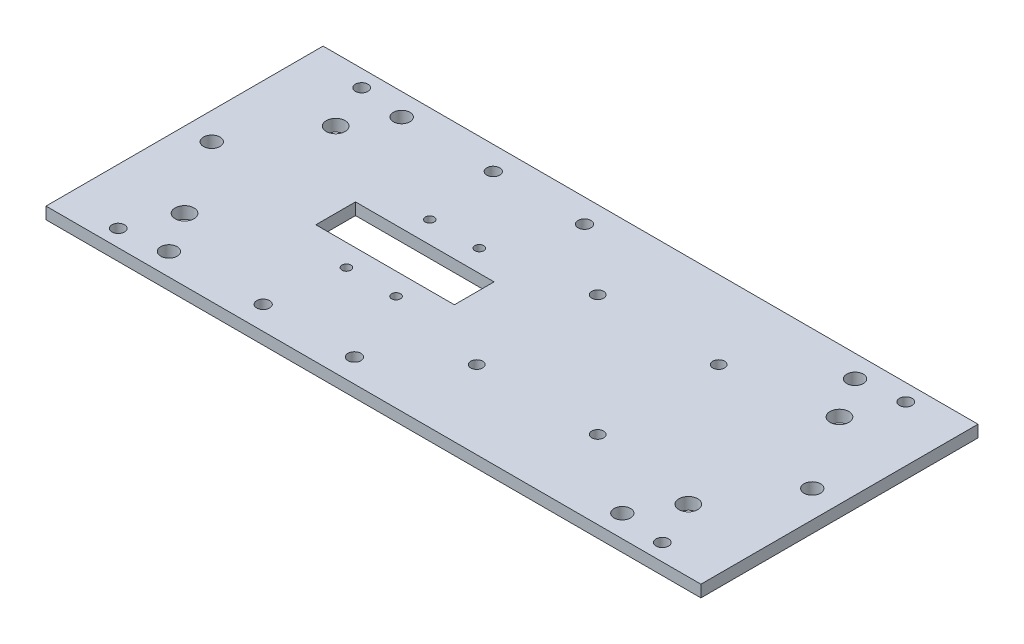
SolidWorks part; units mm, degrees
material "Thornel VCB-20 Carbon Cloth"
ref_plane "Front Plane" through (0, 0, 0) normal (0, 0, 1) x (1, 0, 0)
ref_plane "Top Plane" through (0, 0, 0) normal (0, 1, 0) x (1, 0, 0)
ref_plane "Right Plane" through (0, 0, 0) normal (1, 0, 0) x (0, 0, -1)
sketch "Sketch1" plane through (0, 0, 0) normal (0, 1, 0) x (1, 0, 0)
  line L0 (82.55, -34.925) -> (82.55, 34.925)
  line L1 (82.55, -34.925) -> (-82.55, -34.925)
  line L2 (82.55, 34.925) -> (-82.55, 34.925)
  line L3 (-82.55, -34.925) -> (-82.55, 34.925)
  line L4 (82.55, -34.925) -> (-82.55, 34.925) construction
  line L5 (82.55, 34.925) -> (-82.55, -34.925) construction
  point P1 (0, 0)
  dimension "D1" = 165.1
  dimension "D2" = 69.85
extrude "Boss-Extrude1" add sketch "Sketch1" along normal blind 3
sketch "Sketch6" plane through (0, 0, 0) normal (0, -1, 0) x (1, 0, 0)
  line L0 (-82.55, -34.925) -> (-82.55, 34.925) construction
  line L1 (-44.45, 5) -> (-9.525, 5)
  line L2 (-44.45, 5) -> (-44.45, -5)
  line L3 (-44.45, -5) -> (-9.525, -5)
  line L4 (-9.525, 5) -> (-9.525, -5)
  line L5 (-10.724, -29) -> (-33.726, -29) construction
  line L6 (-10.724, -29) -> (-10.724, 29) construction
  line L7 (-10.724, 29) -> (-33.726, 29) construction
  line L8 (-33.726, -29) -> (-33.726, 29) construction
  line L9 (-10.724, -29) -> (-33.726, 29) construction
  line L10 (-10.724, 29) -> (-33.726, -29) construction
  circle A0 centre (6.35, 15.25) radius 1.5
  circle A1 centre (36.85, 15.25) radius 1.5
  circle A2 centre (6.35, -15.25) radius 1.5
  circle A3 centre (36.85, -15.25) radius 1.5
  circle A4 centre (-33.726, 29) radius 1.625
  circle A5 centre (-10.724, 29) radius 1.625
  circle A6 centre (-10.724, -29) radius 1.625
  circle A7 centre (-33.726, -29) radius 1.625
  point P8 (-9.525, 0)
  point P18 (-22.225, 0)
  dimension "D5" = 3
  dimension "D6" = 3
  dimension "D7" = 3
  dimension "D8" = 3
  dimension "D18" = 3.25
  dimension "D1" = 34.925
  dimension "D2" = 10
  dimension "D3" = 38.1
  dimension "D4" = 30.5
  dimension "D9" = 30.5
  dimension "D10" = 30.5
  dimension "D11" = 15.25
  dimension "D12" = 6.35
  dimension "D13" = 15.25
  dimension "D14" = 15.25
  dimension "D15" = 15.25
  dimension "D16" = 58
  dimension "D17" = 23.002
  dimension "D19" = 60.325
  dimension "D20" = 0
extrude "Cut-Extrude1" cut sketch "Sketch6" against normal up to next contours A4 | L4 L1 L2 L3 A4 | A6 | A2 | A3 | A1 | A0 | A7 | A5 region at (-26.9875, 0, 0) region at (6.35, 0, 15.25) region at (36.85, 0, 15.25) region at (6.35, 0, -15.25) region at (36.85, 0, -15.25) region at (-33.726, 0, 29) region at (-10.724, 0, -29)
sketch "Sketch7" plane through (0, 3, 0) normal (0, 1, 0) x (1, 0, 0)
  line L0 (-82.55, 34.925) -> (-82.55, -34.925) construction
  line L1 (82.55, -34.925) -> (82.55, 34.925) construction
  line L2 (-82.55, -34.925) -> (82.55, -34.925) construction
  line L3 (82.55, 34.925) -> (-82.55, 34.925) construction
  circle A0 centre (-77.47, 29.845) radius 1.5
  circle A1 centre (-77.47, -29.845) radius 1.5
  circle A2 centre (77.47, -29.845) radius 1.5
  circle A3 centre (77.47, 29.845) radius 1.5
  dimension "D9" = 3
  dimension "D10" = 3
  dimension "D11" = 3
  dimension "D12" = 3
  dimension "D1" = 5.08
  dimension "D2" = 5.08
  dimension "D3" = 5.08
  dimension "D4" = 5.08
  dimension "D5" = 5.08
  dimension "D6" = 5.08
  dimension "D7" = 5.08
  dimension "D8" = 5.08
sketch "Sketch8" plane through (0, 3, 0) normal (0, 1, 0) x (1, 0, 0)
  line L0 (-82.55, -34.925) -> (82.55, -34.925) construction
  line L1 (-82.55, 34.925) -> (-82.55, -34.925) construction
  line L2 (82.55, -34.925) -> (82.55, 34.925) construction
  line L3 (82.55, 34.925) -> (-82.55, 34.925) construction
  circle A0 centre (-63.5, -19.05) radius 2.3813
  circle A1 centre (-63.5, 19.05) radius 2.3813
  circle A2 centre (63.5, 19.05) radius 2.3813
  circle A3 centre (63.5, -19.05) radius 2.3813
  dimension "D1" = 4.7625
  dimension "D4" = 4.7625
  dimension "D5" = 4.7625
  dimension "D6" = 4.7625
  dimension "D2" = 15.875
  dimension "D3" = 19.05
  dimension "D7" = 19.05
  dimension "D8" = 19.05
  dimension "D9" = 19.05
  dimension "D10" = 15.875
  dimension "D11" = 15.875
  dimension "D12" = 15.875
extrude "Cut-Extrude3" cut sketch "Sketch8" against normal up to next
sketch "Sketch9" plane through (0, 3, 0) normal (0, 1, 0) x (1, 0, 0)
  line L0 (-82.55, 34.925) -> (-82.55, -34.925) construction
  line L1 (82.55, -34.925) -> (82.55, 34.925) construction
  circle A0 centre (-75.692, 0) radius 2.0828
  circle A1 centre (75.692, 0) radius 2.0828
  dimension "D1" = 6.858
  dimension "D2" = 6.858
extrude "Cut-Extrude5" cut sketch "Sketch9" against normal blind 5.08
sketch "Sketch10" plane through (0, 3, 0) normal (0, 1, 0) x (1, 0, 0)
  line L0 (-82.55, -34.925) -> (82.55, -34.925) construction
  line L1 (82.55, 34.925) -> (-82.55, 34.925) construction
  circle A0 centre (0, -29.337) radius 2.0828
  circle A1 centre (0, 29.337) radius 2.0828
  circle A2 centre (57.15, -29.337) radius 2.0828
  circle A3 centre (57.15, 29.337) radius 2.0828
  circle A4 centre (-57.15, -29.337) radius 2.0828
  circle A5 centre (-57.15, 29.337) radius 2.0828
  point P8 (0, 0)
  dimension "D1" = 5.588
  dimension "D2" = 5.588
  dimension "D3" = 2
  dimension "D4" = 2
extrude "Cut-Extrude6" cut sketch "Sketch10" against normal blind 5.08 contours A5 | A2 | A3 | A4 region at (57.15, 3, 29.337) region at (57.15, 3, -29.337) region at (-57.15, 3, 29.337) region at (-57.15, 3, -29.337)
sketch "Sketch11" plane through (0, 3, 0) normal (0, 1, 0) x (1, 0, 0)
  line L1 (-18.7375, 10.5) -> (-31.2375, 10.5) construction
  line L2 (-18.7375, 10.5) -> (-18.7375, -10.5) construction
  line L3 (-18.7375, -10.5) -> (-31.2375, -10.5) construction
  line L4 (-31.2375, 10.5) -> (-31.2375, -10.5) construction
  line L5 (-18.7375, 10.5) -> (-31.2375, -10.5) construction
  line L6 (-18.7375, -10.5) -> (-31.2375, 10.5) construction
  line L7 (-9.525, 5) -> (-44.45, 5) construction
  circle A0 centre (-31.2375, 10.5) radius 1.125
  circle A1 centre (-18.7375, 10.5) radius 1.125
  circle A2 centre (-18.7375, -10.5) radius 1.125
  circle A3 centre (-31.2375, -10.5) radius 1.125
  point P0 (-24.9875, 0)
  point P9 (-26.9875, 5)
  dimension "D4" = 2.25
  dimension "D5" = 2.25
  dimension "D6" = 2.25
  dimension "D7" = 2.25
  dimension "D1" = 12.5
  dimension "D2" = 21
  dimension "D3" = 2
extrude "Cut-Extrude7" cut sketch "Sketch11" against normal blind 41.91
sketch "Sketch12" plane through (0, 0, 0) normal (0, -1, 0) x (1, 0, 0)
  line L0 (-24.5963, 23.3735) -> (-5.5463, 23.3735) construction
  line L1 (-24.5963, 24.5641) -> (-5.5463, 24.5641)
  line L2 (-24.5963, 24.5641) -> (-24.5963, 22.1829)
  line L3 (-24.5963, 22.1829) -> (-5.5463, 22.1829)
  line L4 (-5.5463, 24.5641) -> (-5.5463, 22.1829)
  line L5 (-15.0713, 24.5641) -> (-15.0713, 22.1829)
  line L6 (0.8037, 24.5641) -> (0.8037, 22.1829)
  line L7 (0.8037, 24.5641) -> (19.8537, 24.5641)
  line L8 (19.8537, 24.5641) -> (19.8537, 22.1829)
  line L9 (0.8037, 22.1829) -> (19.8537, 22.1829)
  line L10 (26.2037, 24.5641) -> (26.2037, 22.1829)
  line L11 (26.2037, 24.5641) -> (45.2537, 24.5641)
  line L12 (45.2537, 24.5641) -> (45.2537, 22.1829)
  line L13 (26.2037, 22.1829) -> (45.2537, 22.1829)
  line L14 (0.8037, 9.3241) -> (0.8037, 6.9429)
  line L15 (0.8037, 9.3241) -> (19.8537, 9.3241)
  line L16 (19.8537, 9.3241) -> (19.8537, 6.9429)
  line L17 (0.8037, 6.9429) -> (19.8537, 6.9429)
  line L18 (26.2037, 9.3241) -> (26.2037, 6.9429)
  line L19 (26.2037, 9.3241) -> (45.2537, 9.3241)
  line L20 (45.2537, 9.3241) -> (45.2537, 6.9429)
  line L21 (26.2037, 6.9429) -> (45.2537, 6.9429)
  line L22 (-24.5963, 9.3241) -> (-24.5963, 6.9429)
  line L23 (-24.5963, 9.3241) -> (-5.5463, 9.3241)
  line L24 (-5.5463, 9.3241) -> (-5.5463, 6.9429)
  line L25 (-24.5963, 6.9429) -> (-5.5463, 6.9429)
  line L26 (-24.5963, 24.5641) -> (0.8037, 24.5641) construction
  line L27 (-71.2714, 9.2531) -> (-61.3765, 9.2531)
  line L28 (-24.5963, -24.8071) -> (0.8037, -24.8071) construction
  line L29 (-24.5963, -23.6165) -> (-5.5463, -23.6165) construction
  line L30 (-24.5963, -7.1859) -> (-5.5463, -7.1859)
  line L31 (-5.5463, -9.5671) -> (-5.5463, -7.1859)
  line L32 (-24.5963, -9.5671) -> (-5.5463, -9.5671)
  line L33 (-24.5963, -9.5671) -> (-24.5963, -7.1859)
  line L34 (26.2037, -7.1859) -> (45.2537, -7.1859)
  line L35 (45.2537, -9.5671) -> (45.2537, -7.1859)
  line L36 (26.2037, -9.5671) -> (45.2537, -9.5671)
  line L37 (26.2037, -9.5671) -> (26.2037, -7.1859)
  line L38 (0.8037, -7.1859) -> (19.8537, -7.1859)
  line L39 (19.8537, -9.5671) -> (19.8537, -7.1859)
  line L40 (0.8037, -9.5671) -> (19.8537, -9.5671)
  line L41 (0.8037, -9.5671) -> (0.8037, -7.1859)
  line L42 (26.2037, -22.4259) -> (45.2537, -22.4259)
  line L43 (45.2537, -24.8071) -> (45.2537, -22.4259)
  line L44 (26.2037, -24.8071) -> (45.2537, -24.8071)
  line L45 (26.2037, -24.8071) -> (26.2037, -22.4259)
  line L46 (0.8037, -22.4259) -> (19.8537, -22.4259)
  line L47 (19.8537, -24.8071) -> (19.8537, -22.4259)
  line L48 (0.8037, -24.8071) -> (19.8537, -24.8071)
  line L49 (0.8037, -24.8071) -> (0.8037, -22.4259)
  line L50 (-15.0713, -24.8071) -> (-15.0713, -22.4259)
  line L51 (-5.5463, -24.8071) -> (-5.5463, -22.4259)
  line L52 (-24.5963, -22.4259) -> (-5.5463, -22.4259)
  line L53 (-24.5963, -24.8071) -> (-24.5963, -22.4259)
  line L54 (-24.5963, -24.8071) -> (-5.5463, -24.8071)
  line L56 (-3.1651, 10.991) -> (-1.5776, 10.991)
  line L57 (-3.1651, 10.991) -> (-3.1651, 20.516)
  line L58 (-3.1651, 20.516) -> (-1.5776, 20.516)
  line L59 (-1.5776, 10.991) -> (-1.5776, 20.516)
  line L60 (-3.1651, 10.991) -> (-1.5776, 20.516) construction
  line L61 (-3.1651, 20.516) -> (-1.5776, 10.991) construction
  line L66 (-3.1651, -20.759) -> (-1.5776, -20.759)
  line L67 (-1.5776, -11.234) -> (-1.5776, -20.759)
  line L68 (-3.1651, -11.234) -> (-1.5776, -11.234)
  line L69 (-3.1651, -11.234) -> (-3.1651, -20.759)
  line L78 (51.6896, 8.9006) -> (51.6896, 6.5194)
  line L79 (51.6896, 8.9006) -> (70.7396, 8.9006)
  line L80 (70.7396, 8.9006) -> (70.7396, 6.5194)
  line L81 (51.6896, 6.5194) -> (70.7396, 6.5194)
  line L82 (-70.3121, -11.1231) -> (-60.4172, -11.1231)
  line L83 (64.3896, -0.545) -> (-18.1604, -0.545) construction
  line L84 (-70.3121, -11.1231) -> (-70.3121, -9.3903)
  line L85 (51.6896, -7.6094) -> (70.7396, -7.6094)
  line L86 (70.7396, -9.9906) -> (70.7396, -7.6094)
  line L87 (51.6896, -9.9906) -> (70.7396, -9.9906)
  line L88 (51.6896, -9.9906) -> (51.6896, -7.6094)
  line L93 (73.1208, 10.5675) -> (73.1208, 20.0925)
  line L94 (47.7208, 10.5675) -> (49.3083, 10.5675)
  line L95 (47.7208, 10.5675) -> (47.7208, 20.0925)
  line L96 (47.7208, 20.0925) -> (49.3083, 20.0925)
  line L97 (49.3083, 10.5675) -> (49.3083, 20.0925)
  line L98 (47.7208, 10.5675) -> (49.3083, 20.0925) construction
  line L99 (47.7208, 20.0925) -> (49.3083, 10.5675) construction
  line L100 (73.1208, 10.5675) -> (74.7083, 10.5675)
  line L101 (74.7083, 10.5675) -> (74.7083, 20.0925)
  line L102 (73.1208, 20.0925) -> (74.7083, 20.0925)
  line L103 (47.7208, 10.5675) -> (73.1208, 10.5675) construction
  line L104 (47.7208, -21.1825) -> (49.3083, -21.1825)
  line L105 (49.3083, -11.6575) -> (49.3083, -21.1825)
  line L106 (47.7208, -11.6575) -> (49.3083, -11.6575)
  line L107 (47.7208, -11.6575) -> (47.7208, -21.1825)
  line L108 (73.1208, -11.6575) -> (74.7083, -11.6575)
  line L109 (74.7083, -11.6575) -> (74.7083, -21.1825)
  line L110 (73.1208, -21.1825) -> (74.7083, -21.1825)
  line L111 (73.1208, -11.6575) -> (73.1208, -21.1825)
  line L112 (-70.3121, -9.3903) -> (-60.4172, -9.3903)
  line L113 (-60.4172, -11.1231) -> (-60.4172, -9.3903)
  line L114 (-52.8291, -27.8715) -> (-33.7791, -27.8715)
  line L115 (-33.7791, -30.2527) -> (-33.7791, -27.8715)
  line L116 (-52.8291, -30.2527) -> (-33.7791, -30.2527)
  line L117 (-52.8291, -30.2527) -> (-52.8291, -27.8715)
  line L118 (-70.3121, -11.1231) -> (-60.4172, -9.3903) construction
  line L123 (-59.3265, -23.1262) -> (-57.739, -23.1262)
  line L124 (-57.739, -13.6012) -> (-57.739, -23.1262)
  line L125 (-59.3265, -13.6012) -> (-57.739, -13.6012)
  line L126 (-59.3265, -13.6012) -> (-59.3265, -23.1262)
  line L127 (-31.3979, -16.6796) -> (-29.8104, -16.6796)
  line L128 (-29.8104, -16.6796) -> (-29.8104, -26.2046)
  line L129 (-31.3979, -26.2046) -> (-29.8104, -26.2046)
  line L130 (-31.3979, -16.6796) -> (-31.3979, -26.2046)
  line L131 (-70.3121, -9.3903) -> (-60.4172, -11.1231) construction
  line L132 (-71.2714, 9.2531) -> (-71.2714, 10.9859)
  line L133 (-31.3979, 16.4366) -> (-31.3979, 25.9616)
  line L134 (-31.3979, 25.9616) -> (-29.8104, 25.9616)
  line L135 (-29.8104, 16.4366) -> (-29.8104, 25.9616)
  line L136 (-31.3979, 16.4366) -> (-29.8104, 16.4366)
  line L137 (-59.5464, 13.798) -> (-59.5464, 23.323)
  line L138 (-59.5464, 13.798) -> (-57.9589, 13.798)
  line L139 (-57.9589, 13.798) -> (-57.9589, 23.323)
  line L140 (-59.5464, 23.323) -> (-57.9589, 23.323)
  line L145 (-71.2714, 10.9859) -> (-61.3765, 10.9859)
  line L146 (-52.8291, 30.0097) -> (-52.8291, 27.6285)
  line L147 (-52.8291, 30.0097) -> (-33.7791, 30.0097)
  line L148 (-33.7791, 30.0097) -> (-33.7791, 27.6285)
  line L149 (-52.8291, 27.6285) -> (-33.7791, 27.6285)
  line L150 (-61.3765, 9.2531) -> (-61.3765, 10.9859)
  point P8 (-65.3646, -10.2567)
  point P60 (-2.3713, 15.7535)
  point P100 (48.5146, 15.33)
  dimension "D1" = 19.05
  dimension "D2" = 2.3813
  dimension "D3" = 25.4
  dimension "D4" = 15.24
  dimension "D5" = 1.5875
  dimension "D6" = 3.175
  dimension "D7" = 9.525
  dimension "D8" = 7.62
extrude "Cut-Extrude8" [suppressed] cut sketch "Sketch12" against normal blind 21.336 contours L37 L36 L35 L34 | L88 L87 L86 L85 | L45 L44 L43 L42 | L117 L116 L115 L114 | L78 L81 L80 L79 | L10 L13 L12 L11 | L6 L9 L8 L7 | L14 L17 L16 L15 | L107 L104 L105 L106 | L109 L110 L111 L108 | L40 L39 L38 L41 | L48 L47 L46 L49 | L67 L66 L69 L68 | L52 L51 L54 L53 | L30 L31 L32 L33 | L130 L129 L128 L127 | L126 L123 L124 L125 | L93 L102 L101 L100 | L97 L96 L95 L94 | L19 L20 L21 L18 | L56 L59 L58 L57 | L25 L24 L23 L22 | L3 L4 L1 L2 | L135 L134 L133 L136 | L149 L148 L147 L146 | L139 L140 L137 L138 | L27 L150 L145 L132 | L84 L82 L113 L112
sketch "Sketch13" plane through (0, 0, 0) normal (0, -1, 0) x (1, 0, 0)
  line L0 (0, 18.4306) -> (0, -15.755) construction
  circle A0 centre (-68.5804, 30.6896) radius 1.5875 construction
  circle A1 centre (-68.5804, -30.6896) radius 1.5875 construction
  circle A2 centre (-68.5804, 30.6896) radius 1.5875
  circle A3 centre (-68.5804, -30.6896) radius 1.5875
  circle A4 centre (68.5804, -30.6896) radius 1.5875
  circle A5 centre (68.5804, 30.6896) radius 1.5875
extrude "Cut-Extrude10" cut sketch "Sketch13" against normal blind 28.034
